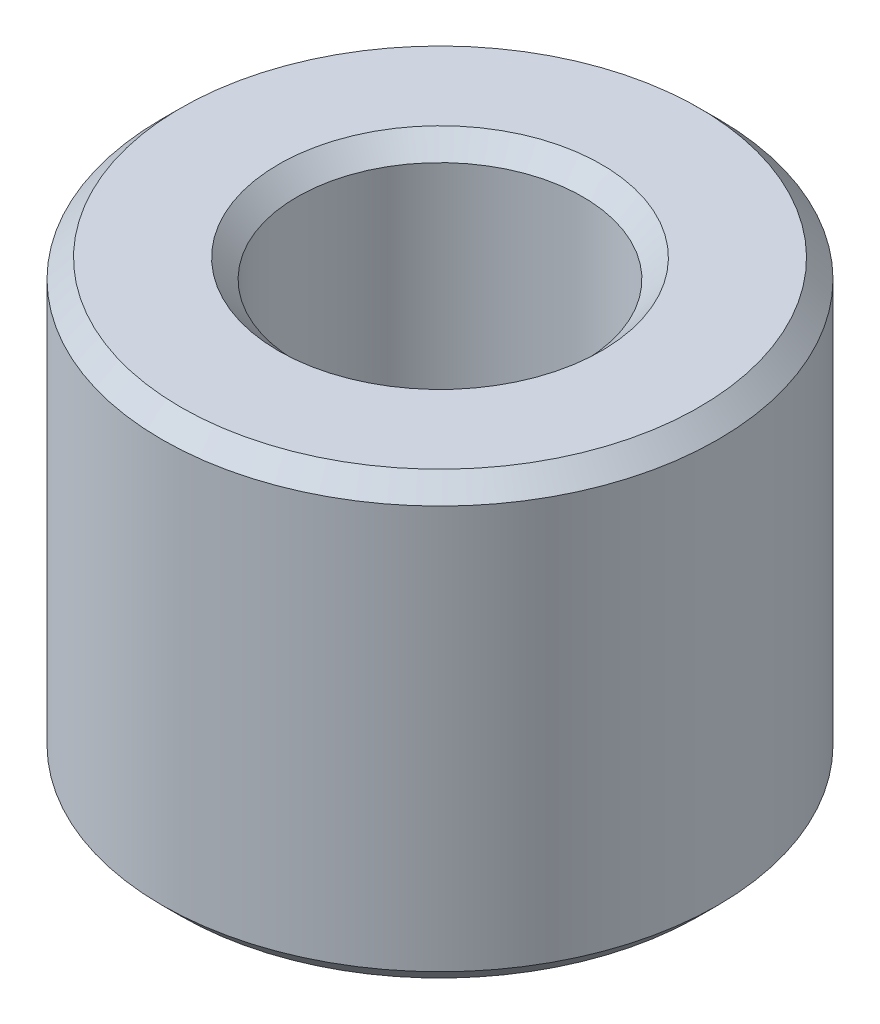
SolidWorks part; units mm, degrees
ref_plane "Front Plane" through (0, 0, 0) normal (0, 0, 1) x (1, 0, 0)
ref_plane "Top Plane" through (0, 0, 0) normal (0, 1, 0) x (1, 0, 0)
ref_plane "Right Plane" through (0, 0, 0) normal (1, 0, 0) x (0, 0, -1)
sketch "Sketch1" plane through (0, 0, 0) normal (0, 1, 0) x (1, 0, 0)
  circle A0 centre (0, 0) radius 32.5
  dimension "SLEEVE_OD" = 65
extrude "Boss-Extrude1" add sketch "Sketch1" along normal blind 51.5386
sketch "Sketch2" plane through (0, 0, 0) normal (0, 1, 0) x (1, 0, 0)
  circle A0 centre (0, 0) radius 16.7011
  dimension "BORE_D" = 33.4022
extrude "Cut-Extrude1" cut sketch "Sketch2" along normal through all
chamfer "Chamfer1" distance 2.1896 angle 45 4 edges at (0, 51.5386, 16.7011) (0, 0, 16.7011) (0, 0, 32.5) (0, 51.5386, 32.5)
